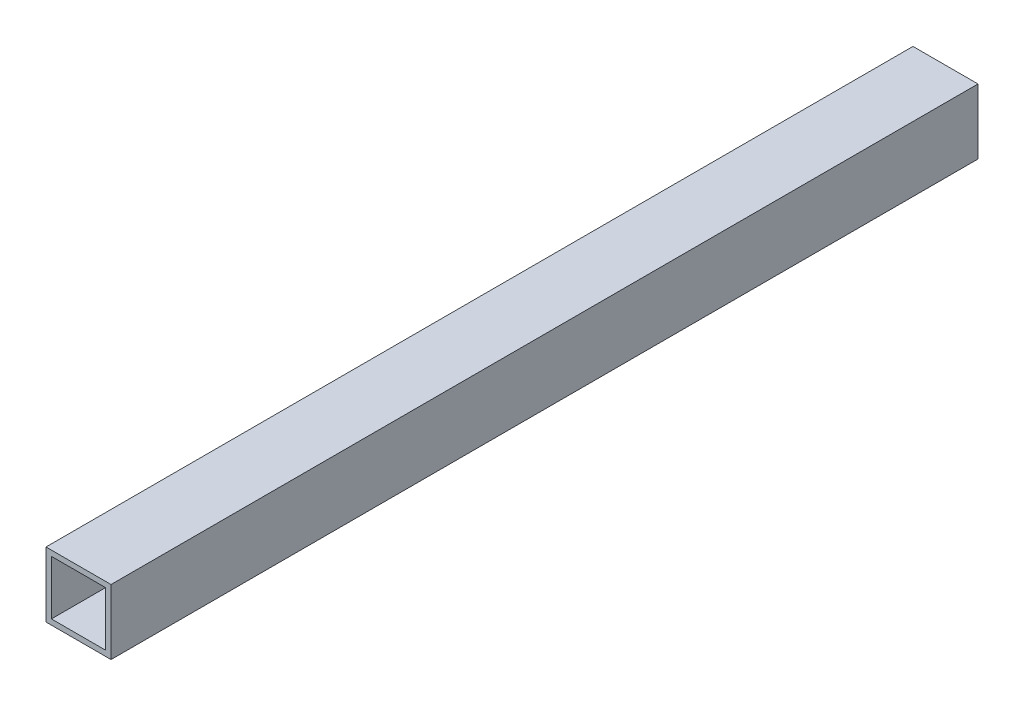
SolidWorks part; units mm, degrees
material "6061-T6 (SS)"
ref_plane "Front" through (0, 0, 0) normal (0, 0, 1) x (1, 0, 0)
ref_plane "Top" through (0, 0, 0) normal (0, 1, 0) x (1, 0, 0)
ref_plane "Right" through (0, 0, 0) normal (1, 0, 0) x (0, 0, -1)
sketch "Sketch1" plane through (0, 0, 0) normal (0, 0, 1) x (1, 0, 0)
  line L0 (-12.5, -12.5) -> (-12.5, 12.5)
  line L1 (-15, -15) -> (15, -15)
  line L2 (-15, -15) -> (-15, 15)
  line L3 (-15, 15) -> (15, 15)
  line L4 (15, -15) -> (15, 15)
  line L5 (-15, -15) -> (15, 15) construction
  line L6 (-15, 15) -> (15, -15) construction
  line L7 (-12.5, 12.5) -> (12.5, 12.5)
  line L8 (12.5, -12.5) -> (12.5, 12.5)
  line L9 (-12.5, -12.5) -> (12.5, -12.5)
  point P0 (0, 0)
  dimension "D2" = 30
  dimension "D1" = 2.5
extrude "Boss-Extrude1" add sketch "Sketch1" along normal mid plane 400
